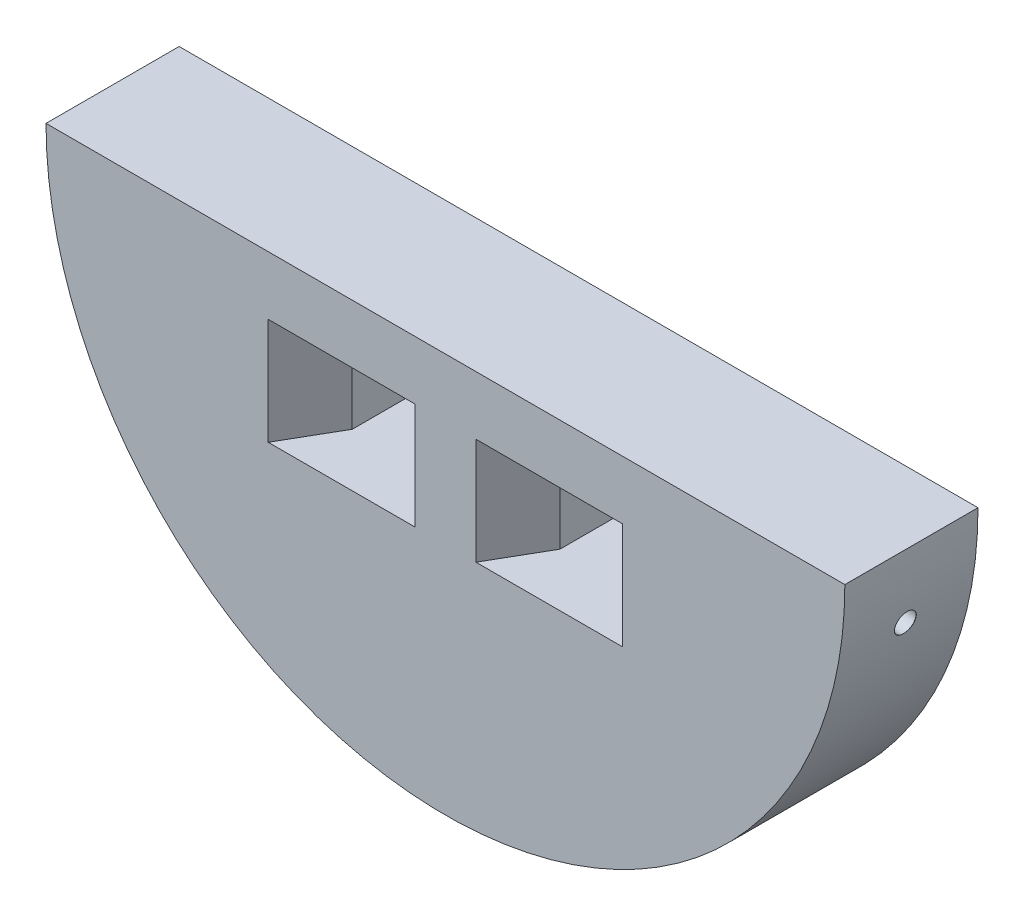
SolidWorks part; units mm, degrees
ref_plane "Front Plane" through (0, 0, 0) normal (0, 0, 1) x (1, 0, 0)
ref_plane "Top Plane" through (0, 0, 0) normal (0, 1, 0) x (1, 0, 0)
ref_plane "Right Plane" through (0, 0, 0) normal (1, 0, 0) x (0, 0, -1)
sketch "Sketch1" plane through (0, 0, 0) normal (0, 0, 1) x (1, 0, 0)
  line L0 (-150, 0) -> (0, 0)
  line L3 (-63.5, -31) -> (-47.5, -31)
  line L4 (-63.5, -31) -> (-63.5, -15)
  line L5 (-63.5, -15) -> (-47.5, -15)
  line L6 (-47.5, -31) -> (-47.5, -15)
  line L7 (-102.5, -31) -> (-86.5, -31)
  line L8 (-102.5, -31) -> (-102.5, -15)
  line L9 (-102.5, -15) -> (-86.5, -15)
  line L10 (-86.5, -31) -> (-86.5, -15)
  arc A1 (-150, 0) -> (0, 0) centre (-75, 0) ccw
  point P0 (-94.5, -15)
  point P13 (-55.5, -15)
  dimension "D1" = 19.5
  dimension "D7" = 75
  dimension "D2" = 15
  dimension "D3" = 19.5
  dimension "D4" = 16
extrude "Boss-Extrude1" add sketch "Sketch1" along normal blind 25
hole_wizard "Ø4.0mm Dowel Hole2" positions "3DSketch2" profile "Sketch4" hole size "Ø4.0" standard "ANSI Metric"
sketch3d "3DSketch2"
  line L2 (0, 0, 25) -> (0, 0, 0) construction
  line L4 (0, 0, 25) -> (0, 0, 0) construction
  line L5 (0, 0, 12.5) -> (-1.1394, -13.0236, 12.5) construction
  line L8 (-75, 0, 0) -> (-75, 0, 25) construction
  line L9 (0, 0, 0) -> (-150, 0, 0) construction
  line L10 (0, 0, 25) -> (-150, 0, 25) construction
  line L12 (-75, 0, 12.5) -> (-1.1394, -13.0236, 12.5) construction
  line L16 (-75, 0, 12.5) -> (0, 0, 12.5) construction
  point P0 (-1.1394, -13.0236, 12.5)
  point P16 (-1.1394, -13.0236, 12.5)
  point P23 (-1.1394, -13.0236, 12.5)
  point P25 (-1.1394, -13.0236, 12.5)
  dimension "D1" = 10
sketch "Sketch4" plane through (-1.1394, -13.0236, 12.5) normal (0, 0, 1) x (0.1736, 0.9848, 0)
  line L0 (0, 0) -> (0, 17.2017)
  line L1 (0, 17.2017) -> (2, 16)
  line L2 (2, 16) -> (2, 0.025)
  line L3 (2, 0.025) -> (2.025, 0)
  line L5 (2.025, 0) -> (0, 0)
  line L6 (-2, 0.025) -> (-2.025, 0) construction
  line L10 (0, 17.2017) -> (-2, 16) construction
  line L11 (0, -6.35) -> (0, 107.95) construction
  dimension "Hole Dia." = 4
  dimension "Hole Depth" = 16
  dimension "Near C'Sink Dia." = 4.05
  dimension "Near C'Sink Angle" = 90
  dimension "Drill Angle" = 118
pattern_circular "CirPattern1" count 5 over 160 about axis through (-75, 0, 0) along (0, 0, 1) of "Ø4.0mm Dowel Hole2" reverse direction yes
chamfer "Chamfer1" distance 15 angle 30 2 edges at (-94.5, -15, 0) (-55.5, -15, 0) first distance on face at (-94.5, -15, 12.5) first distance on face at (-55.5, -15, 12.5)
chamfer "Chamfer3" distance 10 angle 30 4 edges at (-102.5, -23, 25) (-86.5, -23, 25) (-47.5, -23, 25) (-63.5, -23, 25) first distance on face at (-102.5, -19.6679, 13) first distance on face at (-86.5, -19.6679, 13) first distance on face at (-47.5, -19.6679, 13) first distance on face at (-63.5, -19.6679, 13)
chamfer "Chamfer4" distance 4 angle 60 2 edges at (-55.5, -15, 25) (-94.5, -15, 25) first distance on face at (-75, -37.5, 25)
